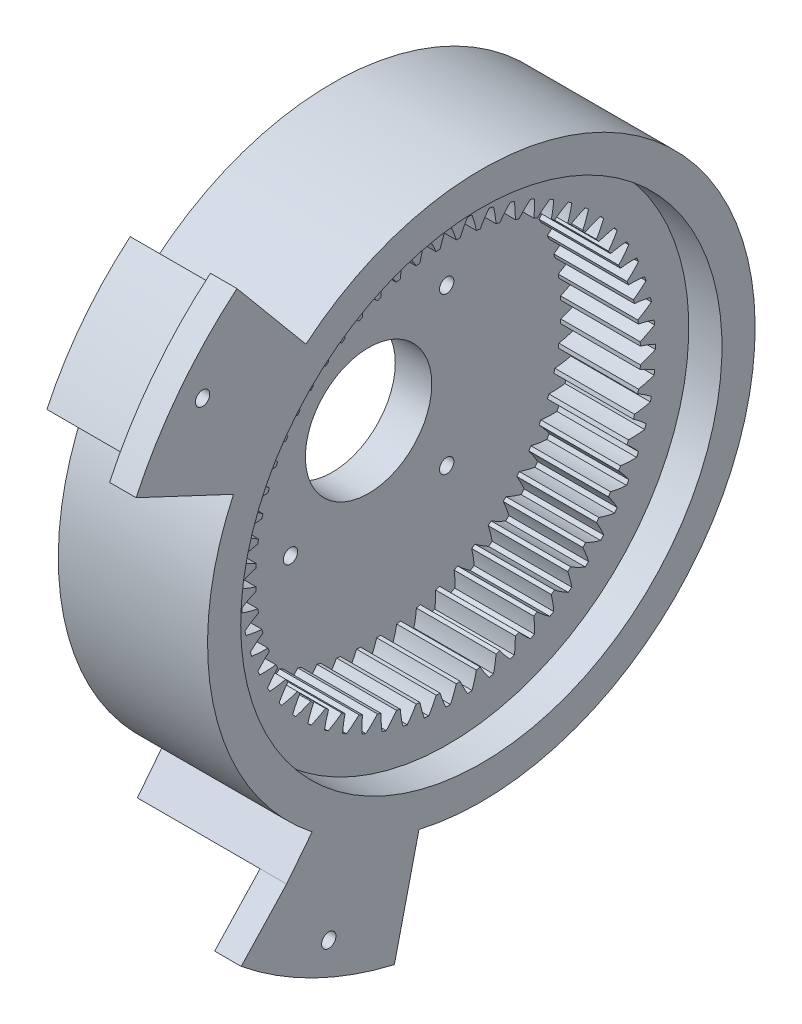
SolidWorks part; units mm, degrees
ref_plane "Plane1" through (0, 0, 0) normal (0, 0, 1) x (1, 0, 0)
ref_plane "Plane2" through (0, 0, 0) normal (0, 1, 0) x (1, 0, 0)
ref_plane "Plane3" through (0, 0, 0) normal (1, 0, 0) x (0, 0, -1)
sketch "HoldingSke" plane through (0, 0, 0) normal (0, 1, 0) x (1, 0, 0)
  line L0 (0, 0) -> (0.5, -0.866)
  line L1 (-15, 0) -> (100, 0) construction
  line L2 (0, 0) -> (-2.1039, 2.3779)
  line L3 (0, 0) -> (-11.863, 4.5341)
  line L4 (0, 0) -> (4.318, 7.479)
  line L5 (0, 0) -> (-23.7986, -8.8762)
  line L6 (0, 0) -> (-10.5278, -7.1032)
  line L7 (-2.1039, 2.3779) -> (3.3635, 27.1825)
  line L8 (-76.2, 3.3779) -> (-54.61, 3.3779)
  line L9 (-71.009, 38.7566) -> (-53.1078, 45.2721)
  line L10 (-76.2, 71.12) -> (104.1128, 71.12)
  line L11 (0, 0) -> (-12, 0)
  line L12 (-76.2, 101.6) -> (-76.162, 101.6)
  line L13 (24.9733, 27.94) -> (52.9518, 28.4284)
  line L14 (24.9733, 27.94) -> (24.9743, 27.94)
  line L15 (24.9733, 27.94) -> (100.4006, 29.5858)
  circle A0 centre (0, 0) radius 12.5
  circle A1 centre (0, 0) radius 12.7
  circle A2 centre (0, 0) radius 12.7
  dimension "MHD" = 25.4
  dimension "Hub_dia" = 25.4
  dimension "Diameter" = 25
  dimension "Num_teeth" = 60
  dimension "Pitch" = 1
  dimension "Overall_len" = 25.4
  dimension "Show_teeth" = 60
  dimension "Thickness" = 12.7
  dimension "OAL" = 25.4001
  dimension "T_dim" = 21.59
  dimension "Ap" = 20
  dimension "H" = 19.05
  dimension "Pitch_radius" = 180.3128
  dimension "Width" = 12
  dimension "Backlash" = 0.038
  dimension "Addendum_fac" = 1
  dimension "Dedendum_fac" = 1.25
  dimension "Clearance_fac" = 0.25
  dimension "Dedendum_add" = 0.001
  dimension "Module" = 1
sketch "BasProSke" plane through (0, 0, 0) normal (0, 1, 0) x (1, 0, 0)
  line L0 (-10, 0) -> (60, 0) construction
  line L1 (0, 29) -> (0, 31.2764)
  line L2 (0, 29) -> (12, 29)
  line L3 (12, 29) -> (12, 31.2764)
  line L4 (12, 31.2764) -> (0, 31.2764)
  dimension "Thickness" = 12
  dimension "Diameter" = 62.5528
  dimension "Inside_diameter" = 58
revolve "Base-Revolve" add sketch "BasProSke" angle 360 about L0
sketch "TooCutSke" plane through (0, 0, 0) normal (1, 0, 0) x (0, 0, -1)
  line L3 (0.8803, 29.9871) -> (0.8803, 53.6633) construction
  line L4 (0, 0) -> (0, 59.563) construction
  line L5 (0, 0) -> (-3.576, 68.2339) construction
  line L6 (-13.1633, 24.7167) -> (36.4631, 27.3175) construction
  circle A0 centre (0, 0) radius 30 construction
  circle A1 centre (0, 0) radius 31.251 construction
  circle A2 centre (0, 0) radius 25.3717 construction
  circle A3 centre (0, 0) radius 28.9746 construction
  arc A4 (1.2274, 28.9486) -> (0.3395, 31.2492) centre (-13.1633, 24.7167) ccw
  arc A5 (1.2274, 28.9486) -> (-1.2274, 28.9486) centre (0, 0) ccw
  arc A6 (0.3395, 31.2492) -> (-0.3395, 31.2492) centre (0, 0) ccw
  arc A7 (-0.3395, 31.2492) -> (-1.2274, 28.9486) centre (13.1633, 24.7167) ccw
  dimension "Pitch_dia" = 60
  dimension "Base_dia" = 50.7434
  dimension "Root_dia" = 62.502
  dimension "Overcut_dia" = 57.9492
  dimension "Flank_rad" = 15
  dimension "Half_ang" = 3
  dimension "Half_CT" = 0.8803
extrude "ToothCut" cut sketch "TooCutSke" along normal through all
fillet "Breaks" [suppressed] radius 0.1
fillet "RootFillets" [suppressed] radius 0.251
pattern_circular "TeethCuts" count 60 every 6 about axis through (-10, 0, 0) along (1, 0, 0) of "RootFillets", "Breaks", "ToothCut"
scale "Scale1" scale about centroid uniform scaling yes scale factor 2
sketch "Sketch1" plane through (18, 0, 0) normal (1, 0, 0) x (0, 0, -1)
  circle A0 centre (0, 0) radius 62.5528
extrude "Extrude-Thin1" add sketch "Sketch1" against normal blind 35 separate body thin thin type one direction wall 10
sketch "Sketch2" plane through (-6, 0, 0) normal (-1, 0, 0) x (0, 0, 1)
  circle A0 centre (0, 0) radius 62.5528
extrude "Boss-Extrude1" add sketch "Sketch2" along normal blind 11
sketch "Sketch3" plane through (-6, 0, 0) normal (1, 0, 0) x (0, 0, -1)
  circle A0 centre (0, 0) radius 19.05
  dimension "D1" = 38.1
extrude "Cut-Extrude1" cut sketch "Sketch3" against normal through all
sketch "Sketch5" plane through (-6, 0, 0) normal (1, 0, 0) x (0, 0, -1)
  line L6 (22.0191, 22.0191) -> (-22.0191, -22.0191) construction
  circle A0 centre (-23.55, 23.55) radius 2.165
  circle A1 centre (-23.55, -23.55) radius 2.165
  circle A2 centre (23.55, 23.55) radius 2.165
  circle A3 centre (23.55, -23.55) radius 2.165
  point P0 (0, 0)
  dimension "D1" = 47.1
  dimension "D2" = 47.1
extrude "Cut-Extrude2" cut sketch "Sketch5" against normal through all
sketch "Sketch6" plane through (-17, 0, 0) normal (-1, 0, 0) x (0, 0, 1)
  circle A0 centre (0, 0) radius 82.5528
  circle A1 centre (0, 0) radius 72.5528
  dimension "D1" = 10
extrude "Boss-Extrude2" add sketch "Sketch6" against normal blind 45 separate body
sketch "Sketch8" plane through (28, 0, 0) normal (1, 0, 0) x (0, 0, -1)
  line L0 (-52.8885, 63.3859) -> (-60.863, 72.9431)
  line L1 (-74.7213, 35.0954) -> (-85.9877, 40.3871)
  line L2 (-51.0218, -64.8979) -> (-58.7148, -74.6832)
  line L3 (-18.8144, -80.3802) -> (-21.6512, -92.4999)
  arc A0 (-60.863, 72.9431) -> (-85.9877, 40.3871) centre (0, 0) ccw
  arc A1 (-52.8885, 63.3859) -> (-74.7213, 35.0954) centre (0, 0) ccw
  circle A2 centre (0, 0) radius 82.5528 construction
  arc A3 (-58.7148, -74.6832) -> (-21.6512, -92.4999) centre (0, 0) ccw
  arc A4 (-51.0218, -64.8979) -> (-18.8144, -80.3802) centre (0, 0) ccw
  dimension "D1" = 190
  dimension "D2" = 25
  dimension "D3" = 25
  dimension "D4" = 101.985
extrude "Boss-Extrude3" add sketch "Sketch8" against normal through all
sketch "Sketch9" plane through (28, 0, 0) normal (1, 0, 0) x (0, 0, -1)
  line L1 (-85.9877, 40.3871) -> (-104.0904, 48.8896)
  line L5 (-60.863, 72.9431) -> (-73.6763, 88.2995)
  line L7 (-51.0218, -64.8979) -> (-58.7148, -74.6832) construction
  line L8 (-58.7148, -74.6832) -> (-72.4005, -89.3486)
  line L10 (-21.6512, -92.4999) -> (-26.2093, -111.9735)
  arc A0 (-73.6763, 88.2995) -> (-104.0904, 48.8896) centre (0, 0) ccw
  arc A1 (-58.7148, -74.6832) -> (-21.6512, -92.4999) centre (0, 0) ccw construction
  arc A2 (-60.863, 72.9431) -> (-85.9877, 40.3871) centre (0, 0) ccw
  arc A3 (-72.4005, -89.3486) -> (-26.2093, -111.9735) centre (0, 0) ccw
  arc A4 (-58.7148, -74.6832) -> (-21.6512, -92.4999) centre (0, 0) ccw
extrude "Boss-Extrude4" add sketch "Sketch9" against normal blind 8
sketch "Sketch10" plane through (28, 0, 0) normal (1, 0, 0) x (0, 0, -1)
  line L0 (0, 0) -> (-84.0488, 64.8636) construction
  line L1 (0, 0) -> (-45.9968, -95.6858) construction
  line L2 (-26.2093, -111.9735) -> (-18.8144, -80.3802) construction
  line L3 (-104.0904, 48.8896) -> (-74.7213, 35.0954) construction
  dimension "D1" = 12.5
  dimension "D2" = 12.5
  dimension "D3" = 106.1672
  dimension "D4" = 106.1672
hole_wizard "Ø1.0mm Dowel Hole1" positions "3DSketch1" profile "Sketch11" hole size "Ø1.0" standard "ANSI Metric" end condition through all
sketch3d "3DSketch1"
  point P0 (28, 64.8636, 84.0488)
  point P3 (28, -95.6858, 45.9968)
sketch "Sketch11" plane through (28, 64.8636, 84.0488) normal (0, 1, 0) x (0, 0, -1)
  line L0 (0, 0) -> (0, 45)
  line L1 (0, 45) -> (2.165, 45)
  line L2 (2.165, 45) -> (2.165, 0)
  line L5 (2.165, 0) -> (0, 0)
  line L11 (0, -6.35) -> (0, 107.95) construction
  dimension "Thru Hole Dia." = 4.33
  dimension "Thru Hole Depth" = 45
sketch "Sketch12" plane through (20, 0, 0) normal (-1, 0, 0) x (0, 0, 1)
  circle A0 centre (45.9968, -95.6858) radius 5.5
  circle A1 centre (84.0488, 64.8636) radius 5.5
extrude "Cut-Extrude3" cut sketch "Sketch12" against normal blind 3
equation "' \"Module@HoldingSke\" = 6.35"
equation "' \"Num_teeth@HoldingSke\" = 24"
equation "' \"Ap@HoldingSke\" =  14.5"
equation "' \"Ap@HoldingSke\" = 14.5"
equation "' \"Width@HoldingSke\" = 12"
equation "' \"Diameter@HoldingSke\" = 8 * 25.4"
equation "' \"Show_teeth@HoldingSke\" = 100"
equation "' \"Backlash@HoldingSke\" = 0.009 * 25.4"
equation "' \"Addendum_fac@HoldingSke\" = 1.0"
equation "' \"Dedendum_fac@HoldingSke\" = 1.25"
equation "' \"Dedendum_add@HoldingSke\" = 0.00005 * 25.4"
equation "' \"Clearance_fac@HoldingSke\" = 0.25"
equation "\"Pitch@HoldingSke\" = 1 / \"Module@HoldingSke\" "
equation "\"Overcut_dia@TooCutSke\" = (\"Num_teeth@HoldingSke\" - 2 * \"Addendum_fac@HoldingSke\") / \"Pitch@HoldingSke\" - 0.002 * 25.4"
equation "\"Pitch_dia@TooCutSke\" = \"Num_teeth@HoldingSke\" / \"Pitch@HoldingSke\""
equation "\"Base_dia@TooCutSke\" = \"Num_teeth@HoldingSke\" / \"Pitch@HoldingSke\" * cos((\"Ap@HoldingSke\"  * 3.14159265 / 180)) * 0.90"
equation "\"Root_dia@TooCutSke\" = \"Num_teeth@HoldingSke\"  / \"Pitch@HoldingSke\" + 2 *  \"Dedendum_fac@HoldingSke\"/ \"Pitch@HoldingSke\" + \"Dedendum_add@HoldingSke\" * 2"
equation "\"Half_ang@TooCutSke\" = 180 / \"Num_teeth@HoldingSke\""
equation "\"Half_CT@TooCutSke\" = \"Num_teeth@HoldingSke\" / \"Pitch@HoldingSke\" * sin((3.14159265 / 2 / \"Num_teeth@HoldingSke\")) / 2 + 10 * \"Backlash@HoldingSke\" / 4"
equation "\"Flank_rad@TooCutSke\" = \"Num_teeth@HoldingSke\" / \"Pitch@HoldingSke\" / 4"
equation "\"Radius@RootFillets\"= \"Clearance_fac@HoldingSke\" / \"Pitch@HoldingSke\" + \"Dedendum_add@HoldingSke\""
equation "\"Break_rad@Breaks\" = 0.02 / \"Pitch@HoldingSke\" * 5"
equation "\"Num_teeth@TeethCuts\" = int( \"Show_teeth@HoldingSke\" ) + 1"
equation "\"Num_teeth@TeethCuts\" = ((sgn( \"Num_teeth@TeethCuts\" - \"Num_teeth@HoldingSke\" )-1)*( \"Num_teeth@TeethCuts\" - \"Num_teeth@HoldingSke\" ))/-2+ \"Num_teeth@HoldingSke\""
equation "\"Num_teeth@TeethCuts\" = ((sgn( \"Num_teeth@TeethCuts\" - 2.0)+1)*( \"Num_teeth@TeethCuts\" - 2.0))/2 +2.0"
equation "\"Angle@TeethCuts\" = 360.0 / \"Num_teeth@HoldingSke\""
equation "\"Diameter@BasProSke\" = \"Num_teeth@HoldingSke\"  / \"Pitch@HoldingSke\" + 2 *  \"Dedendum_fac@HoldingSke\"/ \"Pitch@HoldingSke\" + \"Dedendum_add@HoldingSke\" * 2 + 0.002 * 25.4"
equation "\"Diameter@BasProSke\" = ((sgn( \"Diameter@BasProSke\"  - \"Diameter@HoldingSke\" )+1)*( \"Diameter@BasProSke\"  - \"Diameter@HoldingSke\" ))/2 + \"Diameter@HoldingSke\""
equation "\"Inside_diameter@BasProSke\" =  (\"Num_teeth@HoldingSke\" - 2 * \"Addendum_fac@HoldingSke\") / \"Pitch@HoldingSke\" "
equation "\"Thickness@BasProSke\"  = \"Width@HoldingSke\""
